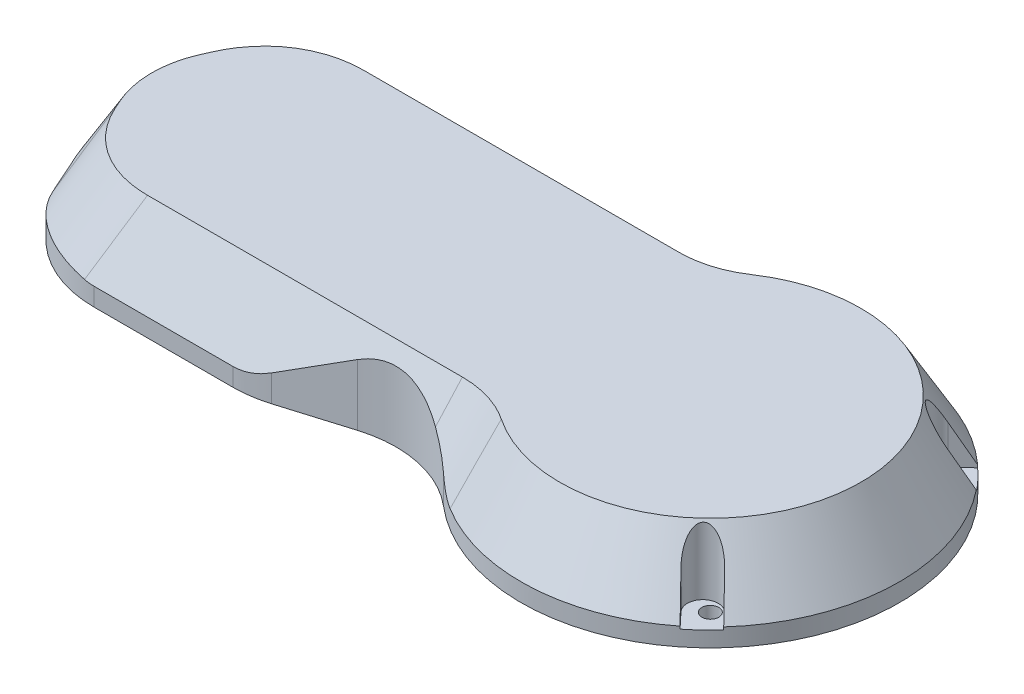
SolidWorks part; units mm, degrees
ref_plane "Front Plane" through (0, 0, 0) normal (0, 0, 1) x (1, 0, 0)
ref_plane "Top Plane" through (0, 0, 0) normal (0, 1, 0) x (1, 0, 0)
ref_plane "Right Plane" through (0, 0, 0) normal (1, 0, 0) x (0, 0, -1)
sketch "Sketch1" plane through (0, 0, 0) normal (0, 1, 0) x (1, 0, 0)
  line L0 (-25.7092, 18.7983) -> (-25.7092, -19.2017) construction
  line L1 (-25.7092, 18.7983) -> (-17.2092, 18.7983) construction
  line L2 (-17.2092, 18.7983) -> (-17.2092, -19.2017) construction
  line L3 (-17.2092, -19.2017) -> (-25.7092, -19.2017) construction
  line L4 (-25.7092, -0.2017) -> (-17.2092, 18.7983)
  line L5 (-25.7092, -0.2017) -> (-17.2092, -19.2017)
  line L6 (-25.7092, -0.2017) -> (53.2908, -0.2017) construction
  line L7 (-17.2092, 18.7983) -> (37.8231, 18.7983)
  line L8 (-17.2092, -19.2017) -> (12.7135, -19.2017)
  line L9 (12.7135, -19.2017) -> (32.5254, -13.2036)
  arc A0 (32.5254, -13.2036) -> (37.8231, 18.7983) centre (53.2908, -0.2017) ccw
  dimension "D4" = 49
  dimension "D1" = 38
  dimension "D2" = 8.5
  dimension "D3" = 79
  dimension "D5" = 20.7
extrude "Boss-Extrude1" add sketch "Sketch1" along normal blind 11
sketch "Sketch2" plane through (0, 11, 0) normal (0, 1, 0) x (1, 0, 0)
  line L0 (-17.2092, 18.7983) -> (-25.7092, -0.2017) construction
  line L1 (39.7169, 13.7983) -> (37.8231, 18.7983) construction
  line L2 (39.7169, 13.7983) -> (-13.9685, 13.7983) construction
  line L3 (37.8231, 18.7983) -> (-17.2092, 18.7983) construction
  line L4 (22.6194, -16.2027) -> (21.1706, -11.4172) construction
  line L5 (12.7135, -19.2017) -> (32.5254, -13.2036) construction
  line L6 (-20.2317, -0.2017) -> (-13.9685, -14.2017) construction
  line L7 (-13.9685, -14.2017) -> (11.9732, -14.2017) construction
  line L8 (21.1706, -11.4172) -> (11.9732, -14.2017) construction
  line L9 (53.2908, -0.2017) -> (3.2908, -0.2017) construction
  line L10 (-20.2317, -0.2017) -> (-13.9685, 13.7983)
  line L11 (-25.7092, -0.2017) -> (-17.2092, -19.2017) construction
  line L12 (21.1706, -11.4172) -> (36.0069, -6.9254) construction
  line L13 (39.7169, 13.7983) -> (-13.9685, 13.7983)
  line L15 (-20.2317, -0.2017) -> (-13.9685, -14.2017)
  line L16 (-13.9685, -14.2017) -> (11.9732, -14.2017)
  line L18 (-17.2092, -19.2017) -> (12.7135, -19.2017) construction
  line L19 (11.9732, -14.2017) -> (39.7169, -14.2017)
  arc A0 (39.7169, -14.2017) -> (39.7169, 13.7983) centre (53.2908, -0.2017) ccw
  circle A1 centre (53.2908, -0.2017) radius 13.5 construction
  circle A2 centre (3.2908, -0.2017) radius 13.5 construction
  dimension "D1" = 39
  dimension "D8" = 27
  dimension "D9" = 27
  dimension "D2" = 5
  dimension "D3" = 50
  dimension "D4" = 5
  dimension "D5" = 5
  dimension "D6" = 5
  dimension "D7" = 5
  dimension "D10" = 5
extrude "Cut-Extrude1" cut sketch "Sketch2" against normal blind 11 draft 30 flip side to cut
fillet "Fillet4" radius 15 4 edges at (-17.2092, 1.1699, -18.7983) (-15.5889, 6.6699, -16.2983) (-15.5889, 6.6699, 16.7017) (-17.2092, 1.1699, 19.2017)
fillet "Fillet5" radius 15 2 edges at (-25.7092, 1.1699, 0.2017) (-22.9705, 6.6699, 0.2017)
fillet "Fillet8" radius 15 2 edges at (37.8231, 1.1699, -18.7983)
fillet "Fillet9" radius 15 1 edges at (32.5254, 5.5, 13.2036)
fillet "Fillet10" radius 15 1 edges
fillet "Fillet11" radius 15 1 edges at (12.7135, 1.1699, 19.2017)
sketch "Sketch3" plane through (0, 0, 0) normal (0, -1, 0) x (1, 0, 0)
  line L0 (53.2908, 0.2017) -> (3.2908, 0.2017) construction
  line L1 (5.2277, -13.2983) -> (5.2277, -18.7983) construction
  line L2 (3.2908, 13.7017) -> (53.2908, 13.7017)
  line L4 (3.2908, -13.2983) -> (53.2908, -13.2983)
  line L5 (33.1848, -18.7983) -> (-7.4871, -18.7983) construction
  arc A0 (53.2908, -13.2983) -> (53.2908, 13.7017) centre (53.2908, 0.2017) ccw
  arc A1 (3.2908, 13.7017) -> (3.2908, -13.2983) centre (3.2908, 0.2017) ccw
  dimension "D2" = 27
  dimension "D3" = 27
  dimension "D1" = 50
  dimension "D4" = 5.5
extrude "Cut-Extrude2" cut sketch "Sketch3" against normal blind 10
sketch "Sketch4" plane through (0, 0, 0) normal (0, -1, 0) x (1, 0, 0)
  line L0 (3.2908, 0.2017) -> (-21.7092, 0.2017) construction
  line L1 (68.6208, 15.5318) -> (53.2908, 0.2017) construction
  line L2 (53.2908, 0.2017) -> (68.6208, -15.1284) construction
  line L3 (68.6208, -15.1284) -> (68.6208, 15.5318) construction
  circle A0 centre (53.2908, 0.2017) radius 21.68 construction
  circle A2 centre (68.6208, 15.5318) radius 1.1
  circle A3 centre (68.6208, -15.1284) radius 1.1
  circle A4 centre (-21.7092, 0.2017) radius 1.1
  dimension "D1" = 43.36
  dimension "D4" = 2.2
  dimension "D5" = 2.2
  dimension "D2" = 25
  dimension "D3" = 45
extrude "Cut-Extrude3" cut sketch "Sketch4" against normal blind 36
sketch "Sketch6" plane through (0, 11, 0) normal (0, 1, 0) x (1, 0, 0)
  line L0 (69.0972, 14.6367) -> (53.2908, -0.2017) construction
  line L1 (53.2908, -0.2017) -> (68.1292, -16.0081) construction
  line L2 (67.7283, 16.0949) -> (71.1646, 19.3208)
  line L3 (71.1646, 19.3208) -> (73.9023, 16.4044)
  line L4 (73.9023, 16.4044) -> (70.466, 13.1786)
  line L5 (66.6711, -17.377) -> (69.7172, -20.6218)
  line L6 (69.7172, -20.6218) -> (72.8284, -18.0917)
  line L7 (72.8284, -18.0917) -> (69.5874, -14.6393)
  circle A0 centre (53.2908, -0.2017) radius 21.68 construction
  arc A1 (67.7283, 16.0949) -> (70.466, 13.1786) centre (69.0972, 14.6367) ccw
  arc A2 (69.5874, -14.6393) -> (66.6711, -17.377) centre (68.1292, -16.0081) ccw
  dimension "D1" = 4
  dimension "D2" = 4
  dimension "D3" = 43.36
extrude "Cut-Extrude5" cut sketch "Sketch6" against normal blind 9
sketch "Sketch7" plane through (0, 11, 0) normal (0, 1, 0) x (1, 0, 0)
  line L1 (-21.7092, 1.7983) -> (-27.3748, 1.7983)
  line L3 (-21.7092, -2.2017) -> (-27.3748, -2.2017)
  line L4 (-27.3748, 1.7983) -> (-27.3748, -2.2017)
  arc A0 (-21.7092, -2.2017) -> (-21.7092, 1.7983) centre (-21.7092, -0.2017) ccw
  dimension "D1" = 4
extrude "Cut-Extrude6" cut sketch "Sketch7" against normal blind 9
